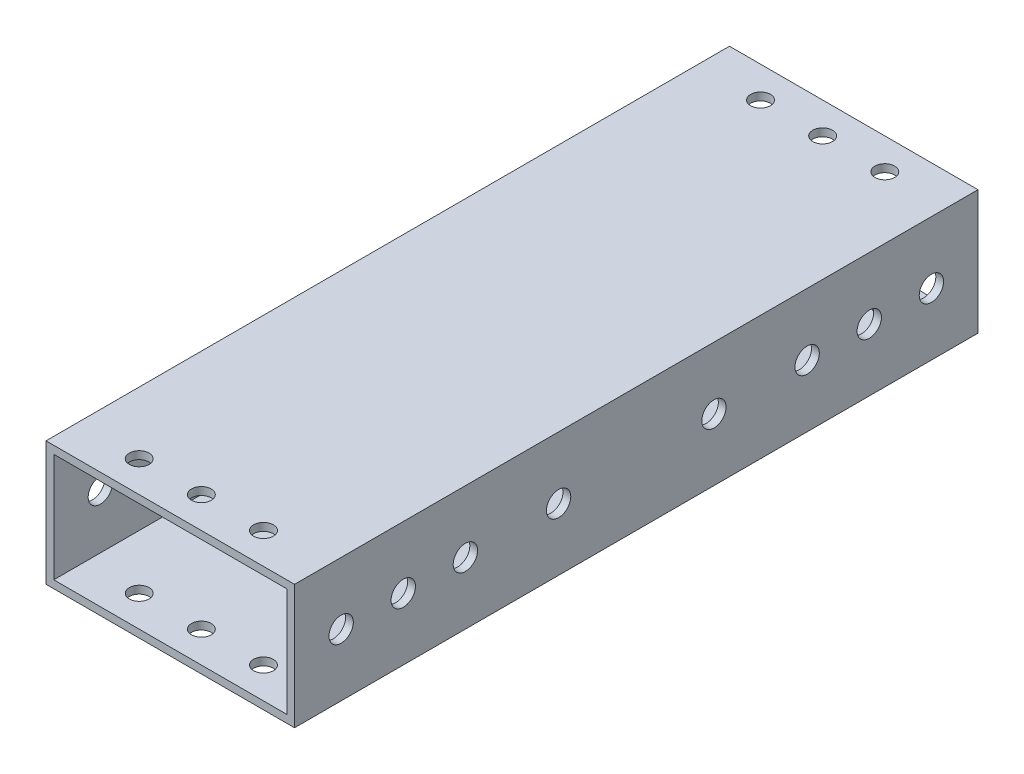
SolidWorks part; units mm, degrees
material "6061-T6 (SS)"
ref_plane "Front Plane" through (0, 0, 0) normal (0, 0, 1) x (1, 0, 0)
ref_plane "Top Plane" through (0, 0, 0) normal (0, 1, 0) x (1, 0, 0)
ref_plane "Right Plane" through (0, 0, 0) normal (1, 0, 0) x (0, 0, -1)
sketch "Sketch1" plane through (0, 0, 0) normal (0, 0, 1) x (1, 0, 0)
  line L0 (-23.8125, 11.1125) -> (23.8125, 11.1125)
  line L1 (-25.4, -12.7) -> (25.4, -12.7)
  line L2 (-25.4, -12.7) -> (-25.4, 12.7)
  line L3 (-25.4, 12.7) -> (25.4, 12.7)
  line L4 (25.4, -12.7) -> (25.4, 12.7)
  line L5 (-25.4, -12.7) -> (25.4, 12.7) construction
  line L6 (-25.4, 12.7) -> (25.4, -12.7) construction
  line L7 (23.8125, -11.1125) -> (23.8125, 11.1125)
  line L8 (-23.8125, -11.1125) -> (23.8125, -11.1125)
  line L9 (-23.8125, -11.1125) -> (-23.8125, 11.1125)
  point P0 (0, 0)
  dimension "D1" = 50.8
  dimension "D2" = 25.4
  dimension "D3" = 1.5875
extrude "Boss-Extrude1" add sketch "Sketch1" along normal mid plane 139.7
sketch "Sketch2" plane through (0, 12.7, 0) normal (0, 1, 0) x (1, 0, 0)
  line L0 (25.4, 69.85) -> (-25.4, 69.85) construction
  line L1 (25.4, 0) -> (-25.4, 0) construction
  line L2 (25.4, -69.85) -> (25.4, 69.85) construction
  line L3 (-25.4, -69.85) -> (-25.4, 69.85) construction
  circle A0 centre (-12.7, 63.5) radius 2.0193
  circle A1 centre (0, 63.5) radius 2.0193
  circle A2 centre (12.7, 63.5) radius 2.0193
  circle A3 centre (12.7, -63.5) radius 2.0193
  circle A4 centre (0, -63.5) radius 2.0193
  circle A5 centre (-12.7, -63.5) radius 2.0193
  dimension "D1" = 4.0386
  dimension "D2" = 12.7
  dimension "D3" = 12.7
  dimension "D4" = 6.35
extrude "Cut-Extrude1" cut sketch "Sketch2" against normal through all
sketch "Sketch3" plane through (25.4, 0, 0) normal (1, 0, 0) x (0, 0, -1)
  line L0 (0, 12.7) -> (0, -12.7) construction
  line L1 (-69.85, 12.7) -> (69.85, 12.7) construction
  line L2 (-69.85, -12.7) -> (69.85, -12.7) construction
  line L3 (-69.85, -12.7) -> (-69.85, 12.7) construction
  circle A0 centre (-60.325, 0) radius 2.4892
  circle A1 centre (60.325, 0) radius 2.4892
  circle A2 centre (-47.625, 0) radius 2.4892
  circle A3 centre (-34.925, 0) radius 2.4892
  circle A4 centre (34.925, 0) radius 2.4892
  circle A5 centre (47.625, 0) radius 2.4892
  circle A6 centre (-15.875, 0) radius 2.4892
  circle A7 centre (15.875, 0) radius 2.4892
  point P23 (0, 0)
  dimension "D1" = 19.05
  dimension "D3" = 4.9784
  dimension "D2" = 9.525
  dimension "D4" = 12.7
  dimension "D5" = 12.7
extrude "Cut-Extrude2" cut sketch "Sketch3" against normal through all
